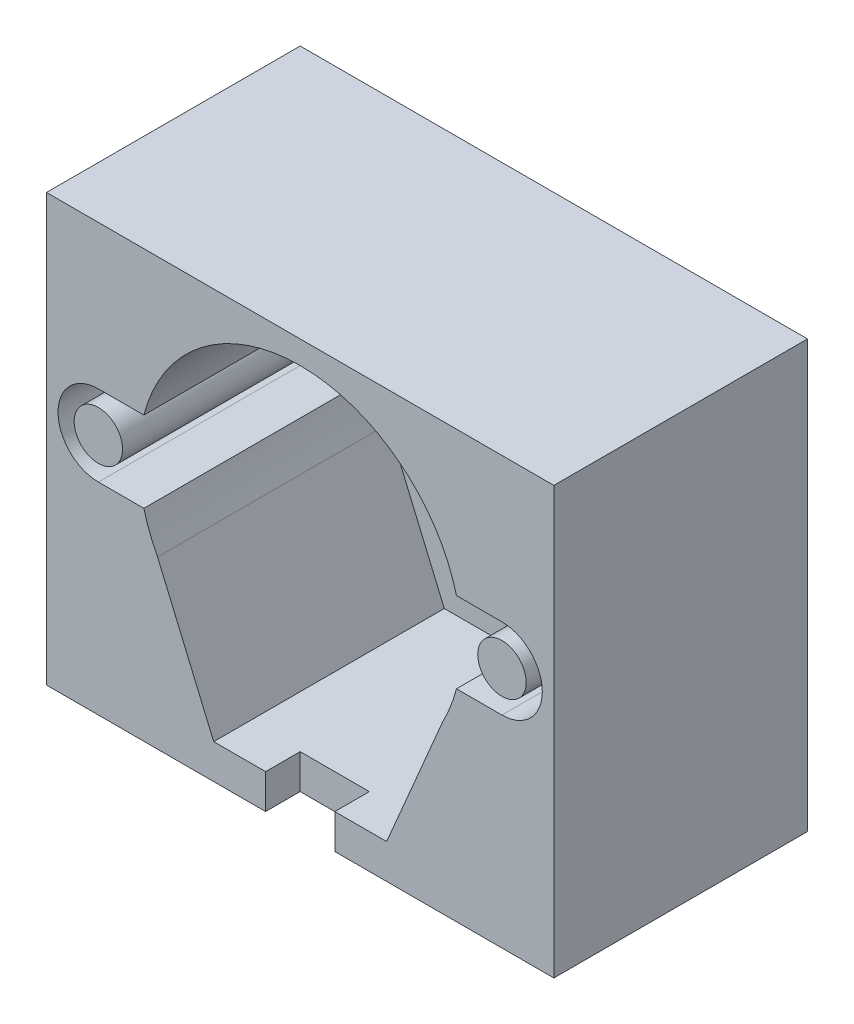
SolidWorks part; units mm, degrees
ref_plane "前视基准面" through (0, 0, 0) normal (0, 0, 1) x (1, 0, 0)
ref_plane "上视基准面" through (0, 0, 0) normal (0, 1, 0) x (1, 0, 0)
ref_plane "右视基准面" through (0, 0, 0) normal (1, 0, 0) x (0, 0, -1)
sketch "草图1" plane through (0, 0, 0) normal (0, 0, 1) x (1, 0, 0)
  line L4 (22, 0) -> (-22, 0)
  line L5 (-22, 0) -> (-22, 37)
  line L6 (-22, 37) -> (22, 37)
  line L7 (22, 37) -> (22, 0)
  point P2 (0, 0)
  dimension "D1" = 37
  dimension "D2" = 44
extrude "凸台-拉伸1" add sketch "草图1" along normal blind 22
sketch "草图2" plane through (0, 0, 22) normal (0, 0, 1) x (1, 0, 0)
  line L0 (0, 37) -> (0, 0) construction
  line L1 (22, 37) -> (-22, 37) construction
  line L2 (-7.5, 3) -> (7.5, 3)
  line L3 (-7.5, 3) -> (-12.3678, 14.4398)
  line L4 (7.5, 3) -> (12.3678, 14.4398)
  line L5 (-17.5, 24.5) -> (-13.5554, 24.5)
  line L6 (-17.5, 17.5) -> (-13.5554, 17.5)
  line L7 (17.5, 17.5) -> (13.5554, 17.5)
  line L8 (17.5, 24.5) -> (13.5554, 24.5)
  arc A0 (-13.5554, 17.5) -> (-12.3678, 14.4398) centre (0, 21) ccw
  circle A1 centre (-17.5, 21) radius 2.1
  circle A3 centre (17.5, 21) radius 2.1
  arc A5 (-17.5, 24.5) -> (-17.5, 17.5) centre (-17.5, 21) ccw
  arc A6 (17.5, 24.5) -> (17.5, 17.5) centre (17.5, 21) cw
  arc A7 (13.5554, 24.5) -> (-13.5554, 24.5) centre (0, 21) ccw
  arc A8 (12.3678, 14.4398) -> (13.5554, 17.5) centre (0, 21) ccw
  point P7 (0, 3)
  dimension "D4" = 28
  dimension "D8" = 4.2
  dimension "D1" = 7
  dimension "D2" = 34
  dimension "D3" = 18
  dimension "D5" = 17.5
extrude "切除-拉伸7" cut sketch "草图2" against normal blind 20
sketch "草图10" plane through (0, 0, 0) normal (0, 0, -1) x (-1, 0, 0)
  line L0 (-22, 37) -> (22, 37) construction
  line L1 (0, 37) -> (0, 29)
  dimension "D1" = 8
ref_point "点2"
ref_axis "基准轴3" through (0, 29, 0) along (0, 0, 1)
sketch "草图13" plane through (0, 0, 0) normal (0, 0, -1) x (-1, 0, 0)
  circle A0 centre (0, 20.9143) radius 8
  point P2 (0, 0)
  point P3 (0, 20.9143)
  dimension "D1" = 16
extrude "切除-拉伸11" cut sketch "草图13" against normal through all
sketch "草图15" plane through (0, 0, 0) normal (0, -1, 0) x (1, 0, 0)
  line L0 (-22, 22) -> (22, 22) construction
  line L1 (-3, 22) -> (3, 22)
  line L2 (-3, 22) -> (-3, 19)
  line L3 (-3, 19) -> (3, 19)
  line L4 (3, 22) -> (3, 19)
  line L5 (0, 0) -> (0, 18.9714) construction
  dimension "D1" = 3
  dimension "D2" = 6
  dimension "D3" = 3
extrude "切除-拉伸13" cut sketch "草图15" against normal up to next
